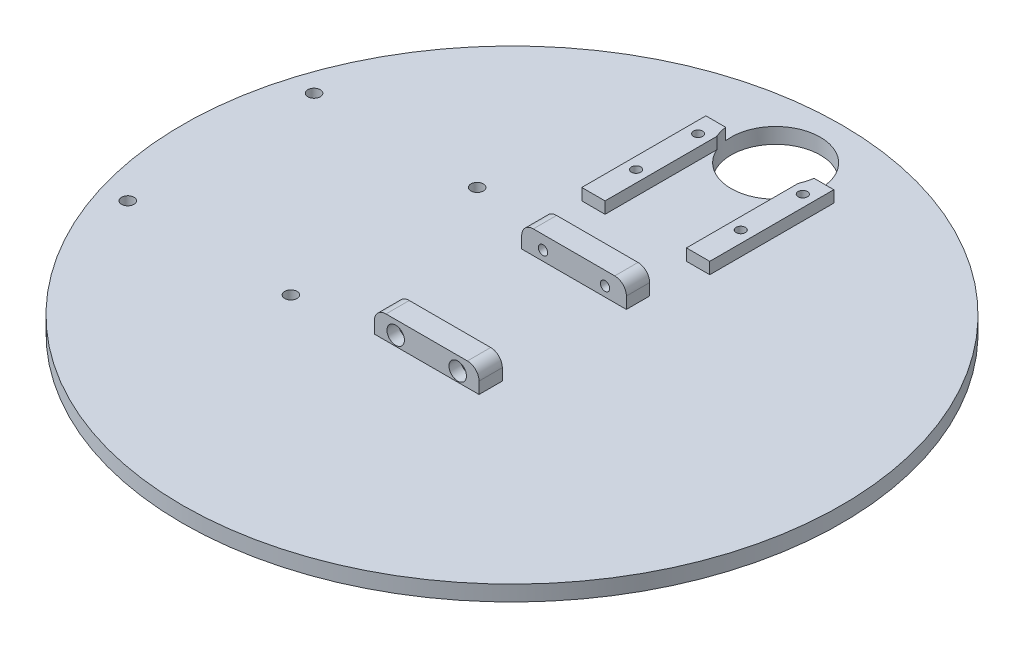
SolidWorks part; units mm, degrees
ref_plane "Front Plane" through (0, 0, 0) normal (0, 0, 1) x (1, 0, 0)
ref_plane "Top Plane" through (0, 0, 0) normal (0, 1, 0) x (1, 0, 0)
ref_plane "Right Plane" through (0, 0, 0) normal (1, 0, 0) x (0, 0, -1)
sketch "Sketch1" plane through (0, 0, 0) normal (0, 1, 0) x (1, 0, 0)
  circle A0 centre (0, 0) radius 32.65
  circle A1 centre (0, 0) radius 37.65
  dimension "D1" = 65.3
  dimension "D2" = 5
extrude "Boss-Extrude1" add sketch "Sketch1" along normal blind 10
sketch "Sketch2" plane through (0, 10, 0) normal (0, 1, 0) x (1, 0, 0)
  circle A0 centre (0, 0) radius 29.65
  circle A1 centre (0, 0) radius 32.65 construction
  circle A2 centre (0, 0) radius 32.65
  dimension "D1" = 3
extrude "Boss-Extrude2" add sketch "Sketch2" against normal blind 4
sketch "Sketch3" plane through (0, 10, 0) normal (0, 1, 0) x (1, 0, 0)
  circle A0 centre (0, 0) radius 85
  dimension "D1" = 170
extrude "Boss-Extrude3" add sketch "Sketch3" along normal blind 4
sketch "Sketch4" plane through (0, 14, 0) normal (0, 1, 0) x (1, 0, 0)
  line L0 (0, 0) -> (-32.7045, 0) construction
  line L1 (-13.5, 16) -> (13.5, 16)
  line L2 (-13.5, 16) -> (-13.5, 22)
  line L3 (-13.5, 22) -> (13.5, 22)
  line L4 (13.5, 16) -> (13.5, 22)
  line L5 (0, 0) -> (0, 16) construction
  dimension "D1" = 6
  dimension "D2" = 32
  dimension "D3" = 27
extrude "Boss-Extrude4" add sketch "Sketch4" along normal blind 6
fillet "Fillet1" radius 3 2 edges at (-13.5, 20, -19) (13.5, 20, -19)
sketch "Sketch6" plane through (0, 0, -22) normal (0, 0, -1) x (-1, 0, 0)
  line L0 (0, 14) -> (0, 20) construction
  line L1 (-13.5, 14) -> (13.5, 14) construction
  line L2 (-10.5, 20) -> (10.5, 20) construction
  circle A0 centre (-8, 16.5) radius 2.25
  circle A1 centre (8, 16.5) radius 2.25
  dimension "D2" = 4.5
  dimension "D1" = 16
  dimension "D3" = 2.5
extrude "Cut-Extrude1" cut sketch "Sketch6" against normal blind 3
hole_wizard "CSK for M2 Countersunk Flat Head Screw1" positions "3DSketch1" profile "Sketch5" countersink size "M2" standard "ISO" end condition through all
sketch3d "3DSketch1"
  line L8 (8, 16.5, -19) -> (8, 16.5, -22) construction
  line L9 (-8, 16.5, -19) -> (-8, 16.5, -22) construction
  point P21 (8, 16.5, -19)
  point P25 (-8, 16.5, -19)
sketch "Sketch5" plane through (8, 16.5, -19) normal (1, 0, 0) x (0, 1, 0)
  line L0 (0, 0) -> (0, 104)
  line L1 (0, 104) -> (1.2, 104)
  line L2 (1.2, 104) -> (1.2, 1)
  line L3 (1.2, 1) -> (2.2, 0)
  line L5 (2.2, 0) -> (0, 0)
  line L6 (-1.2, 1) -> (-2.2, 0) construction
  line L11 (0, -6.35) -> (0, 107.95) construction
  dimension "Thru Hole Dia." = 2.4
  dimension "Thru Hole Depth" = 104
  dimension "Near C'Sink Dia." = 4.4
  dimension "Near C'Sink Angle" = 90
mirror "Mirror1" about plane through (0, 0, 0) normal (0, 0, 1) of "CSK for M2 Countersunk Flat Head Screw1", "Fillet1", "Boss-Extrude4", "Cut-Extrude1"
sketch "Sketch8" plane through (0, 10, 0) normal (0, -1, 0) x (-1, 0, 0)
  line L0 (0, 85) -> (0, 22) construction
  line L1 (-5.75, 22) -> (-10.25, 22) construction
  circle A0 centre (0, 0) radius 85 construction
  circle A2 centre (13.5, 61.5) radius 2.25
  dimension "D2" = 4.5
  dimension "D1" = 39.5
  dimension "D3" = 27
extrude "Cut-Extrude2" cut sketch "Sketch8" against normal blind 4
sketch "Sketch11" plane through (0, 14, 0) normal (0, 1, 0) x (1, 0, 0)
  line L0 (-13.5, 61.5) -> (-13.5, 66.5) construction
  line L1 (-16.5, 66.5) -> (-10.5, 66.5)
  line L2 (-16.5, 66.5) -> (-16.5, 50.5)
  line L3 (-16.5, 50.5) -> (-10.5, 50.5)
  line L4 (-10.5, 66.5) -> (-10.5, 50.5)
  dimension "D1" = 5
  dimension "D2" = 16
  dimension "D3" = 6
extrude "Boss-Extrude5" add sketch "Sketch11" along normal blind 3
hole_wizard "CSK for M2 Countersunk Flat Head Screw2" positions "3DSketch2" profile "Sketch9" countersink size "M2" standard "ISO" end condition through all
sketch3d "3DSketch2"
  line L0 (-13.5, 14, -61.5) -> (-13.5, 10, -61.5) construction
  point P7 (-13.5, 14, -61.5)
sketch "Sketch9" plane through (-13.5, 14, -61.5) normal (1, 0, 0) x (0, 0, -1)
  line L0 (0, 0) -> (0, 6)
  line L1 (0, 6) -> (1.2, 6)
  line L2 (1.2, 6) -> (1.2, 1)
  line L3 (1.2, 1) -> (2.2, 0)
  line L5 (2.2, 0) -> (0, 0)
  line L6 (-1.2, 1) -> (-2.2, 0) construction
  line L11 (0, -6.35) -> (0, 107.95) construction
  dimension "Thru Hole Dia." = 2.4
  dimension "Thru Hole Depth" = 6
  dimension "Near C'Sink Dia." = 4.4
  dimension "Near C'Sink Angle" = 90
mirror "Mirror2" about plane through (0, 0, 0) normal (1, 0, 0) of "Boss-Extrude5", "CSK for M2 Countersunk Flat Head Screw2", "Cut-Extrude2"
pattern_linear "LPattern1" count 2 spacing 16 along (0, 0, 1) of "Mirror2"
sketch "Sketch12" plane through (0, 14, 0) normal (0, 1, 0) x (1, 0, 0)
  line L0 (0, 68) -> (0, 22) construction
  line L1 (13.5, 22) -> (-13.5, 22) construction
  circle A0 centre (0, 68) radius 11.5
  dimension "D1" = 46
  dimension "24" = 23
extrude "Cut-Extrude3" cut sketch "Sketch12" against normal through all and the other way through all
hole_wizard "CSK for M3 Countersunk Flat Head Screw1" positions "3DSketch4" profile "Sketch14" countersink size "M3" standard "ISO" end condition through all
sketch3d "3DSketch4"
  line L1 (-75.07, 10, 24.02) -> (-75.07, 10, -24.02) construction
  line L2 (-75.07, 10, 24.02) -> (-33, 10, 24.02) construction
  line L3 (-33, 10, 24.02) -> (-33, 10, -24.02) construction
  line L4 (-75.07, 10, -24.02) -> (-33, 10, -24.02) construction
  line L11 (-33, 10, 0) -> (0, 10, 0) construction
  line L12 (0, 6, 0) -> (0, 10, 0) construction
  point P0 (-33, 10, -24.02)
  point P2 (-75.07, 10, -24.02)
  point P4 (-75.07, 10, 24.02)
  point P6 (-33, 10, 24.02)
  point P66 (0, 0, 0)
  dimension "D1" = 33
  dimension "D2" = 42.07
  dimension "D3" = 48.04
sketch "Sketch14" plane through (-33, 10, -24.02) normal (1, 0, 0) x (0, 0, -1)
  line L0 (0, 0) -> (0, 10)
  line L1 (0, 10) -> (1.6, 10)
  line L2 (1.6, 10) -> (1.6, 1.55)
  line L3 (1.6, 1.55) -> (3.15, 0)
  line L5 (3.15, 0) -> (0, 0)
  line L6 (-1.6, 1.55) -> (-3.15, 0) construction
  line L11 (0, -6.35) -> (0, 107.95) construction
  dimension "Thru Hole Dia." = 3.2
  dimension "Thru Hole Depth" = 10
  dimension "Near C'Sink Dia." = 6.3
  dimension "Near C'Sink Angle" = 90
